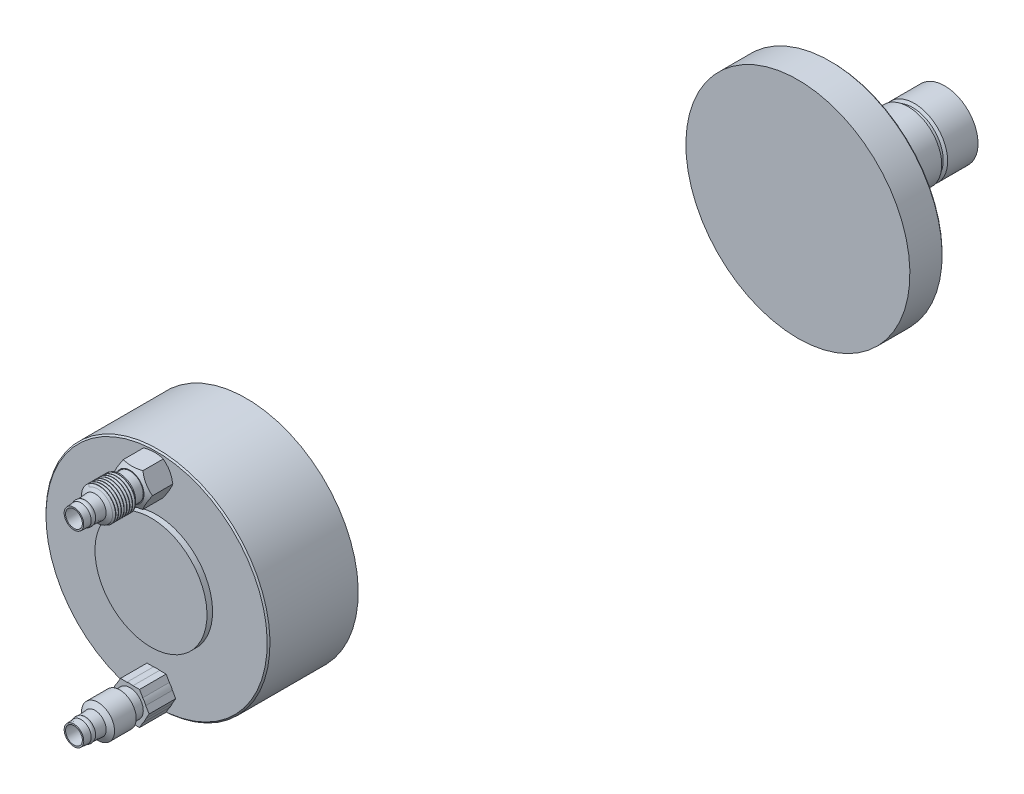
SolidWorks part; units mm, degrees
note: The reader was unsure of these and kept them because the rebuilt part matched: shared geometry of "Эскиз2<4>", "Эскиз2<5>".
ref_plane "Спереди" through (0, 0, 0) normal (0, 0, 1) x (1, 0, 0)
ref_plane "Сверху" through (0, 0, 0) normal (0, 1, 0) x (1, 0, 0)
ref_plane "Справа" through (0, 0, 0) normal (1, 0, 0) x (0, 0, -1)
sketch "Эскиз2" plane through (0, 0, 0) normal (1, 0, 0) x (0, 0, -1)
  line L0 (0, 0) -> (-284, 0) construction
  line L1 (176.3233, 959.2038) -> (2294.3233, 959.2038) construction
  line L2 (-284, 0) -> (-284, 20)
  line L3 (-284, 20) -> (-282, 20)
  line L4 (-282, 20) -> (-282, 39.5)
  line L5 (-282, 39.5) -> (-281.5, 40)
  line L6 (-281.5, 40) -> (-41.5, 40)
  line L7 (-41.5, 40) -> (-41, 39.5)
  line L8 (-41, 39.5) -> (-41, 39)
  line L9 (-41, 39) -> (-27, 39)
  line L10 (-27, 39) -> (-26, 38)
  line L11 (-26, 38) -> (-26, 0)
  line L12 (-26, 0) -> (-26, 12)
  line L13 (-26, 12) -> (-13.6351, 12)
  line L14 (-13.6351, 12) -> (-13, 10.9)
  line L15 (-13, 10.9) -> (-12, 10.9)
  line L16 (-12, 10.9) -> (-11.4226, 11.9)
  line L17 (-11.4226, 11.9) -> (-0.5774, 11.9)
  line L18 (-0.5774, 11.9) -> (0, 10.9)
  line L19 (0, 10.9) -> (0, 0)
  line L20 (-41, 39) -> (-41, 0)
  line L21 (-53, 40) -> (-53, 0)
  line L22 (-284, 0) -> (0, 0)
  line L23 (-250, 40) -> (-250, 0)
  line L24 (-282, 33.5) -> (-317.5677, 33.5) construction
  line L25 (-317.5677, 33.5) -> (-317.5677, 0) construction
  line L26 (-317.5677, 0) -> (-284, 0) construction
  line L27 (-311.5, 33.5) -> (-311.5, 37)
  line L28 (-311.5, 37) -> (-304, 37.5)
  line L29 (-304, 37.5) -> (-304, 39.4)
  line L30 (-304, 39.4) -> (-294.5, 39.4)
  line L31 (-294.5, 39.4) -> (-294.5, 38.25)
  line L32 (-294.5, 38.25) -> (-291.5, 38.25)
  line L33 (-291.5, 38.25) -> (-291.5, 39.5)
  line L34 (-291.5, 39.5) -> (-282, 39.5)
  line L35 (-311.5, -33.5) -> (-311.5, -37)
  line L36 (-311.5, -37) -> (-304, -37.5)
  line L37 (-304, -37.5) -> (-304, -39.4)
  line L38 (-304, -39.4) -> (-294.5, -39.4)
  line L39 (-294.5, -39.4) -> (-294.5, -38.25)
  line L40 (-294.5, -38.25) -> (-291.5, -38.25)
  line L41 (-291.5, -38.25) -> (-291.5, -39.5)
  line L42 (-291.5, -39.5) -> (-282, -39.5)
  line L43 (-282, -33.5) -> (-317.5677, -33.5) construction
  line L44 (-304, 33.5) -> (-282, 33.5)
  line L45 (-311.5, 36.5) -> (-304, 36.5)
  line L46 (-311.5, 36.5) -> (-311.5, 33.5)
  line L47 (-311.5, 33.5) -> (-304, 33.5)
  line L48 (-304, 36.5) -> (-304, 33.5)
  line L49 (-311.5, -33.5) -> (-304, -33.5)
  line L50 (-311.5, -33.5) -> (-311.5, -36.5)
  line L51 (-311.5, -36.5) -> (-304, -36.5)
  line L52 (-304, -33.5) -> (-304, -36.5)
  line L53 (-304, -33.5) -> (-282, -33.5)
  line L54 (-282, -39.5) -> (-282, -33.5)
  line L55 (-282, -33.5) -> (-282.0064, -33.5112)
  line L56 (-282, -33.5) -> (-304, -33.5)
  line L57 (-304, 37.5) -> (-302.903, 39.4)
  line L58 (-302.903, 39.4) -> (-295.164, 39.4)
  line L59 (-295.164, 39.4) -> (-294.5, 38.25)
  line L60 (-294.5, -38.25) -> (-295.164, -39.4)
  line L62 (-304, -37.5) -> (-302.903, -39.4)
  arc A0 (-309, 37.1667) -> (-307.5033, 37.2664) centre (-308.1653, 35.9204) cw
  arc A1 (-309, -37.1667) -> (-307.5033, -37.2664) centre (-308.1653, -35.9204) ccw
  dimension "D34" = 1.5
  dimension "D1" = 284
  dimension "D2" = 30
  dimension "D3" = 120
  dimension "D4" = 120
  dimension "D5" = 23.8
  dimension "D6" = 1
  dimension "D7" = 13
  dimension "D8" = 1
  dimension "D9" = 24
  dimension "D10" = 26
  dimension "D11" = 15
  dimension "D12" = 12
  dimension "D13" = 80
  dimension "D14" = 78
  dimension "D15" = 45
  dimension "D16" = 1
  dimension "D17" = 45
  dimension "D18" = 0.5
  dimension "D19" = 241
  dimension "D20" = 45
  dimension "D21" = 0.5
  dimension "D22" = 40
  dimension "D23" = 34
  dimension "D24" = 33.5
  dimension "D25" = 9.5
  dimension "D26" = 3
  dimension "D27" = 9.5
  dimension "D28" = 7
  dimension "D29" = 8
  dimension "D30" = 7.5
  dimension "D31" = 11.8
  dimension "D32" = 9.5
  dimension "D33" = 1.5
  dimension "D35" = 2.5
  dimension "D36" = 12
  dimension "D37" = 7.5
  dimension "D38" = 3
  dimension "D39" = 7.5
  dimension "D40" = 3
  dimension "D41" = 30
  dimension "D42" = 30
  dimension "D43" = 30
  dimension "D44" = 30
  dimension "D45" = 6
revolve "Повернуть2" add sketch "Эскиз2" angle 360 about L44
revolve "Повернуть3" add sketch "Эскиз2<4>" angle 360 about L43
sketch "Эскиз2<4>" plane through (0, 0, 0) normal (1, 0, 0) x (0, 0, -1) same geometry as "Эскиз2"
revolve "Повернуть4" add sketch "Эскиз2<5>" angle 360 about L26
sketch "Эскиз2<5>" plane through (0, 0, 0) normal (1, 0, 0) x (0, 0, -1) same geometry as "Эскиз2"
sketch "Эскиз4" plane through (0, 0, 282) normal (0, 0, 1) x (1, 0, 0)
  line L0 (0, -33.5) -> (0, -33.5112) construction
  line L1 (3.4641, 39.5) -> (-3.4641, 39.5)
  line L2 (-3.4641, 39.5) -> (-6.9282, 33.5)
  line L3 (-6.9282, 33.5) -> (-3.4641, 27.5)
  line L4 (-3.4641, 27.5) -> (3.4641, 27.5)
  line L5 (3.4641, 27.5) -> (6.9282, 33.5)
  line L6 (6.9282, 33.5) -> (3.4641, 39.5)
  line L7 (3.4096, -27.6) -> (-3.4096, -27.6)
  line L8 (-3.4096, -27.6) -> (-6.8192, -33.5056)
  line L9 (-6.8192, -33.5056) -> (-3.4096, -39.4112)
  line L10 (-3.4096, -39.4112) -> (3.4096, -39.4112)
  line L11 (3.4096, -39.4112) -> (6.8192, -33.5056)
  line L12 (6.8192, -33.5056) -> (3.4096, -27.6)
  circle A0 centre (0, 33.5) radius 6 construction
  circle A1 centre (0, -33.5056) radius 5.9056 construction
  circle A4 centre (0, -33.5) radius 5.9 construction
  dimension "D2" = 12
extrude "Бобышка-Вытянуть1" add sketch "Эскиз4" along normal up to surface (9.5 mm away) up to face at (0, 27.5, 291.5)
sketch "Эскиз5" plane through (0, 0, 0) normal (1, 0, 0) x (0, 0, -1)
  line L0 (-282, 33.5) -> (-317.5677, 33.5) construction
  line L1 (-317.5677, 33.5) -> (-317.5677, -33.5) construction
  line L2 (-317.5677, -33.5) -> (-282, -33.5056) construction
  line L3 (-291.5, 38.5) -> (-282, 38.5) construction
  line L6 (-291.5, 38.25) -> (-291.5, 39.5) construction
  line L7 (-282, 20) -> (-282, 39.5) construction
  line L8 (-291.5, 39.5) -> (-282, 39.5) construction
  line L9 (-291.5, 38.5) -> (-286.75, 46.7272)
  line L11 (-286.75, 46.7272) -> (-282, 38.5)
  line L13 (-282, 38.5) -> (-282, 48.5)
  line L14 (-282, 48.5) -> (-291.5, 48.5)
  line L15 (-291.5, 48.5) -> (-291.5, 38.5)
  line L16 (-284, 0) -> (-340.9928, 0) construction
  line L17 (-284, 20) -> (-284, -20) construction
  line L18 (-291.5, -38.5) -> (-282, -38.5) construction
  line L19 (-282, -33.5) -> (-317.5677, -33.5) construction
  line L20 (-291.5, -48.5) -> (-291.5, -38.5)
  line L21 (-282, -48.5) -> (-291.5, -48.5)
  line L22 (-282, -38.5) -> (-282, -48.5)
  line L23 (-286.75, -46.7272) -> (-282, -38.5)
  line L24 (-291.5, -38.5) -> (-286.75, -46.7272)
  dimension "D1" = 1
  dimension "D2" = 30
  dimension "D3" = 10
revolve "Вырез-Повернуть6" cut sketch "Эскиз5" angle 360 about L24
sketch "Эскиз9" plane through (0, 0, 311.5) normal (0, 0, 1) x (1, 0, 0)
  circle A0 centre (0, 33.5) radius 6
  dimension "D1" = 12
curve "Спираль2" pitch 1 height 18 turns 18
ref_plane "Плоскость2" through (6, 33.5, 311.5) normal (0, -0.9996, -0.0265) x (-1, 0, 0)
sketch "Эскиз10" plane through (6, 33.5, 311.5) normal (0, -0.9996, -0.0265) x (-1, 0, 0)
  line L0 (0, 0) -> (0.8617, -0.4975)
  line L1 (0.8617, -0.4975) -> (0, -0.995)
  line L2 (0, -0.995) -> (0, 0)
  dimension "D1" = 60
  dimension "D2" = 0.995
sweep "Вырез-По траектории2" cut profiles "Эскиз10" path "Спираль2"
sketch "Эскиз11" plane through (0, 0, 282) normal (0, 0, -1) x (-1, 0, 0)
  point P0 (0, 33.5)
